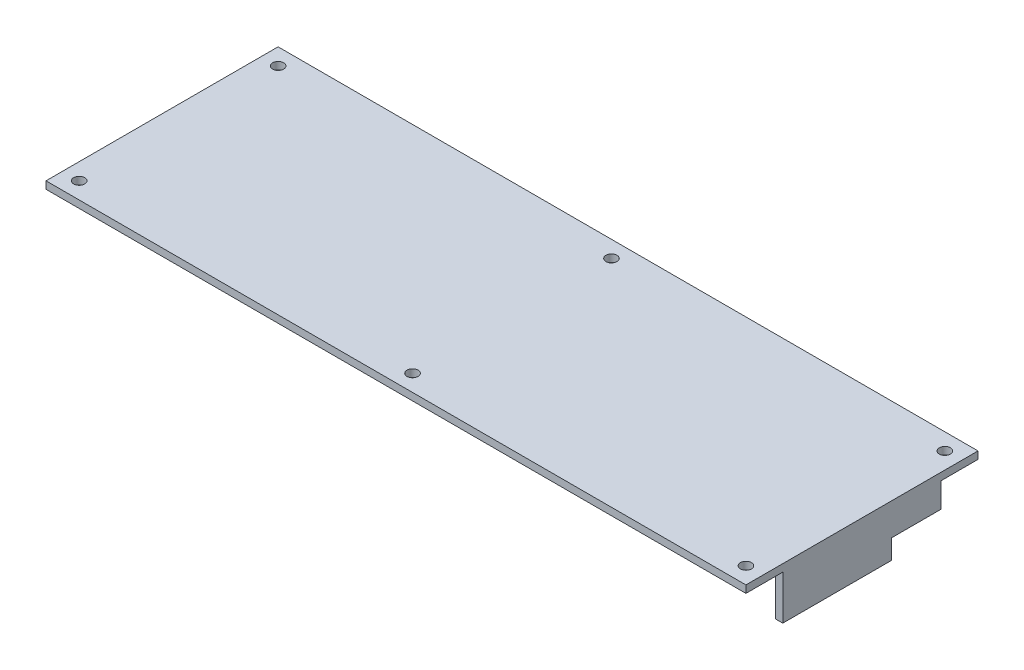
SolidWorks part; units mm, degrees
ref_plane "Front Plane" through (0, 0, 0) normal (0, 0, 1) x (1, 0, 0)
ref_plane "Top Plane" through (0, 0, 0) normal (0, 1, 0) x (1, 0, 0)
ref_plane "Right Plane" through (0, 0, 0) normal (1, 0, 0) x (0, 0, -1)
sketch "Sketch1" plane through (0, 0, 0) normal (0, 1, 0) x (1, 0, 0)
  line L0 (0, 15.9498) -> (0, -13.7203) construction
  line L9 (-95, -31.5) -> (95, -31.5)
  line L10 (-95, -31.5) -> (-95, 31.5)
  line L11 (-95, 31.5) -> (95, 31.5)
  line L12 (95, -31.5) -> (95, 31.5)
  line L13 (-95, -31.5) -> (95, 31.5) construction
  line L14 (-95, 31.5) -> (95, -31.5) construction
  line L15 (-95, 31.5) -> (-86, 31.5)
  line L16 (-95, 31.5) -> (-95, 22.5)
  line L17 (-93, 22.5) -> (-90.5, 22.5)
  line L18 (-86, 29.5) -> (-86, 27)
  line L19 (-23.9463, 0) -> (24.4289, 0) construction
  line L20 (93, 22.5) -> (90.5, 22.5)
  line L21 (86, 29.5) -> (86, 27)
  line L22 (95, 31.5) -> (86, 31.5)
  line L23 (95, 31.5) -> (95, 22.5)
  line L24 (95, -31.5) -> (86, -31.5)
  line L25 (86, -29.5) -> (86, -27)
  line L26 (93, -22.5) -> (90.5, -22.5)
  line L27 (95, -31.5) -> (95, -22.5)
  line L28 (-93, -22.5) -> (-90.5, -22.5)
  line L29 (-86, -29.5) -> (-86, -27)
  line L30 (-95, -31.5) -> (-86, -31.5)
  line L31 (-95, -31.5) -> (-95, -22.5)
  line L35 (-4.5, 31.5) -> (4.5, 31.5)
  line L37 (-4.5, 22.5) -> (4.5, 31.5) construction
  line L38 (-4.5, 31.5) -> (4.5, 22.5) construction
  line L42 (-95, 31.5) -> (-86, 22.5) construction
  line L43 (-95, 22.5) -> (-86, 31.5) construction
  line L44 (92, 29.5981) -> (93.5, 27)
  line L45 (-93.5, 27) -> (-92, 24.4019)
  line L46 (-92, 24.4019) -> (-89, 24.4019)
  line L47 (-89, 24.4019) -> (-87.5, 27)
  line L48 (-87.5, 27) -> (-89, 29.5981)
  line L49 (-89, 29.5981) -> (-92, 29.5981)
  line L50 (-92, 29.5981) -> (-93.5, 27)
  line L51 (89, 29.5981) -> (92, 29.5981)
  line L52 (87.5, 27) -> (89, 29.5981)
  line L53 (89, 24.4019) -> (87.5, 27)
  line L54 (92, 24.4019) -> (89, 24.4019)
  line L55 (93.5, 27) -> (92, 24.4019)
  line L56 (89, -29.5981) -> (92, -29.5981)
  line L57 (87.5, -27) -> (89, -29.5981)
  line L58 (89, -24.4019) -> (87.5, -27)
  line L59 (92, -24.4019) -> (89, -24.4019)
  line L60 (93.5, -27) -> (92, -24.4019)
  line L61 (92, -29.5981) -> (93.5, -27)
  line L62 (-92, -29.5981) -> (-93.5, -27)
  line L63 (-89, -29.5981) -> (-92, -29.5981)
  line L64 (-87.5, -27) -> (-89, -29.5981)
  line L65 (-89, -24.4019) -> (-87.5, -27)
  line L66 (-92, -24.4019) -> (-89, -24.4019)
  line L67 (-93.5, -27) -> (-92, -24.4019)
  line L80 (-4.5, 31.5) -> (-4.5, 22.5) construction
  line L81 (4.5, 31.5) -> (4.5, 22.5) construction
  line L82 (4.5, 22.5) -> (-4.5, 22.5) construction
  line L83 (-4.5, 29.5) -> (-4.5, 27)
  line L84 (4.5, 29.5) -> (4.5, 27)
  line L85 (4.5, -29.5) -> (4.5, -27)
  line L92 (-4.5, -29.5) -> (-4.5, -27)
  line L93 (1.5, -24.4019) -> (3, -27)
  line L94 (3, 27) -> (1.5, 29.5981)
  line L95 (1.5, 29.5981) -> (-1.5, 29.5981)
  line L96 (-1.5, 29.5981) -> (-3, 27)
  line L97 (-3, 27) -> (-1.5, 24.4019)
  line L98 (-1.5, 24.4019) -> (1.5, 24.4019)
  line L99 (1.5, 24.4019) -> (3, 27)
  line L106 (-1.5, -24.4019) -> (1.5, -24.4019)
  line L107 (-3, -27) -> (-1.5, -24.4019)
  line L108 (-1.5, -29.5981) -> (-3, -27)
  line L109 (1.5, -29.5981) -> (-1.5, -29.5981)
  line L110 (3, -27) -> (1.5, -29.5981)
  line L111 (-86, 29.5) -> (-4.5, 29.5)
  line L112 (-93, 22.5) -> (-93, -22.5)
  line L113 (-86, -29.5) -> (-4.5, -29.5)
  line L114 (4.5, -29.5) -> (86, -29.5)
  line L115 (93, -22.5) -> (93, 22.5)
  line L116 (86, 29.5) -> (4.5, 29.5)
  circle A0 centre (-90.5, 27) radius 1.5
  circle A1 centre (-90.5, 27) radius 2.5981 construction
  circle A2 centre (90.5, 27) radius 1.5
  circle A3 centre (90.5, -27) radius 1.5
  circle A4 centre (-90.5, -27) radius 1.5
  circle A5 centre (0, 27) radius 1.5
  circle A6 centre (0, 27) radius 2.5981 construction
  arc A8 (-90.5, 22.5) -> (-86, 27) centre (-90.5, 27) ccw
  arc A9 (-4.5, 27) -> (4.5, 27) centre (0, 27) ccw
  circle A10 centre (0, -27) radius 1.5
  arc A11 (-4.5, -27) -> (4.5, -27) centre (0, -27) cw
  arc A12 (-86, -27) -> (-90.5, -22.5) centre (-90.5, -27) ccw
  arc A13 (86, -27) -> (90.5, -22.5) centre (90.5, -27) cw
  arc A14 (86, 27) -> (90.5, 22.5) centre (90.5, 27) ccw
  point P0 (0, 0)
  point P22 (0, 27)
  point P27 (0, 31.5)
  point P28 (0, 31.5)
  point P91 (-86, -22.5)
  point P94 (86, -22.5)
  point P97 (86, 22.5)
  dimension "D7" = 3
  dimension "D10" = 3
  dimension "D13" = 4.5
  dimension "D14" = 4.5
  dimension "D15" = 4.5
  dimension "D16" = 4.5
  dimension "D17" = 2
  dimension "D11" = 6
  dimension "D1" = 190
  dimension "D2" = 63
  dimension "D3" = 9
  dimension "D4" = 9
  dimension "D5" = 9
  dimension "D6" = 9
  dimension "D8" = 6
  dimension "D9" = 1.5
  dimension "D12" = 1.5
  dimension "D18" = 2
  dimension "D19" = 2
  dimension "D20" = 2
  dimension "D21" = 2
  dimension "D22" = 2
  dimension "D23" = 4.5
  dimension "D24" = 4.5
  dimension "D25" = 2
  dimension "D26" = 2
  dimension "D27" = 2
  dimension "D28" = 2
  dimension "D29" = 4.5
  dimension "D30" = 4.5
  dimension "D31" = 2
  dimension "D32" = 2
extrude "Boss-Extrude1" add sketch "Sketch1" along normal blind 2 contours A14 L21 L116 L84 A9 L83 L111 L18 A8 L17 L112 L28 A12 L29 L113 L92 A11 L85 L114 L25 A13 L26 L115 L20 region at (0, 0, 0)
extrude "Boss-Extrude2" add sketch "Sketch1<4>" along normal blind 19 separate body contours A2 | A3 | A10 | A5 | A0 | A4 region at (-90.5, 0, -27) region at (90.5, 0, -27) region at (90.5, 0, 27) region at (0, 0, -27) region at (0, 0, 27)
sketch "Sketch1<4>" plane through (0, 0, 0) normal (0, 1, 0) x (1, 0, 0) same geometry as "Sketch1"
extrude "Boss-Extrude3" add sketch "Sketch1<5>" along normal blind 20 contours L55 L44 L51 L52 L53 L54 A2 | L56 L61 L60 L59 L58 L57 A3 | L110 L93 L106 L107 L108 L109 A10 | L98 L99 L94 L95 L96 L97 A5 | L67 L62 L63 L64 L65 L66 A4 | L49 L50 L45 L46 L47 L48 A0 region at (92.6813, 0, -28.2594) region at (-92.6813, 0, -28.2594) region at (88.3187, 0, 28.2594) region at (-92.6813, 0, 28.2594) region at (2.1813, 0, 25.7406) region at (2.1813, 0, -25.7406)
sketch "Sketch1<5>" plane through (0, 0, 0) normal (0, 1, 0) x (1, 0, 0) same geometry as "Sketch1"
extrude "Boss-Extrude4" add sketch "Sketch1<6>" along normal blind 22 contours L9 L12 L11 L10 L99 L98 L97 L96 L95 L94 L61 L56 L57 L58 L59 L60 L50 L49 L48 L47 L46 L45 L44 L55 L54 L53 L52 L51 L62 L67 L66 L65 L64 L63 L93 region at (-94.7998, 0, 27)
sketch "Sketch1<6>" plane through (0, 0, 0) normal (0, 1, 0) x (1, 0, 0) same geometry as "Sketch1"
sketch "Sketch2" plane through (95, 0, 0) normal (1, 0, 0) x (0, 0, -1)
  line L0 (-22.5, 2) -> (22.5, 2) construction
  line L1 (-22.5, 12.0332) -> (-22.5, 2) construction
  line L2 (-31.5, 22) -> (-31.5, 0) construction
  line L3 (-31.5, 0) -> (31.5, 0) construction
  line L4 (31.5, 22) -> (31.5, 0) construction
  line L5 (-21.5, 2) -> (1.5, 2)
  line L6 (-21.5, 2) -> (-21.5, 10)
  line L7 (-21.5, 10) -> (1.5, 10)
  line L8 (1.5, 2) -> (1.5, 10)
  line L10 (8, 2) -> (21.5, 2)
  line L11 (8, 2) -> (8, 15.3)
  line L12 (8, 15.3) -> (21.5, 15.3)
  line L13 (21.5, 2) -> (21.5, 15.3)
  dimension "D1" = 9
  dimension "D2" = 2
  dimension "D3" = 9
  dimension "D4" = 23
  dimension "D5" = 8
  dimension "D6" = 10
  dimension "D7" = 13.3
  dimension "D8" = 13.5
  dimension "D9" = 10
extrude "Cut-Extrude1" cut sketch "Sketch2" against normal blind 3
sketch "Sketch3" plane through (0, 0, -31.5) normal (0, 0, -1) x (-1, 0, 0)
  line L0 (-95, 22) -> (-95, 0) construction
  line L1 (-75, 2) -> (-55, 2)
  line L2 (-75, 2) -> (-75, 14)
  line L3 (-75, 14) -> (-55, 14)
  line L4 (-55, 2) -> (-55, 14)
  line L5 (95, 0) -> (-95, 0) construction
  line L6 (95, 22) -> (95, 0) construction
  line L7 (35, 2) -> (68, 2)
  line L8 (35, 2) -> (35, 14)
  line L9 (35, 14) -> (68, 14)
  line L10 (68, 2) -> (68, 14)
  dimension "D1" = 20
  dimension "D2" = 20
  dimension "D3" = 2
  dimension "D4" = 12
  dimension "D5" = 60
  dimension "D6" = 33
  dimension "D7" = 2
  dimension "D8" = 12
extrude "Cut-Extrude2" cut sketch "Sketch3" against normal blind 3
sketch "Sketch4" plane through (-95, 0, 0) normal (-1, 0, 0) x (0, 0, 1)
  line L0 (0, 0) -> (0, 22) construction
  line L1 (31.5, 22) -> (-31.5, 22) construction
  line L2 (31.5, 0) -> (-31.5, 0) construction
  line L3 (-15.5, 2) -> (-3.5, 2)
  line L4 (-15.5, 2) -> (-15.5, 9.5)
  line L5 (-15.5, 9.5) -> (-3.5, 9.5)
  line L6 (-3.5, 2) -> (-3.5, 9.5)
  line L7 (-31.5, 22) -> (-31.5, 0) construction
  line L8 (15.5, 9.5) -> (3.5, 9.5)
  line L9 (3.5, 2) -> (3.5, 9.5)
  line L10 (15.5, 2) -> (3.5, 2)
  line L11 (15.5, 2) -> (15.5, 9.5)
  dimension "D1" = 2
  dimension "D2" = 12
  dimension "D3" = 7.5
  dimension "D4" = 16
extrude "Cut-Extrude3" cut sketch "Sketch4" against normal blind 3
sketch "Sketch5" plane through (95, 0, 0) normal (1, 0, 0) x (0, 0, -1)
  line L0 (-21.5, 10) -> (-21.5, 22)
  line L1 (-31.5, 22) -> (31.5, 22) construction
  line L2 (-21.5, 10) -> (8, 10)
  line L3 (8, 15.3) -> (8, 2) construction
  line L4 (8, 10) -> (8, 15.3)
  line L5 (8, 15.3) -> (21.5, 15.3)
  line L6 (21.5, 15.3) -> (21.5, 22)
  line L7 (-21.5, 22) -> (-31.5, 22)
  line L8 (-31.5, 22) -> (-31.5, 0)
  line L9 (-31.5, 0) -> (31.5, 0)
  line L10 (31.5, 0) -> (31.5, 22)
  line L11 (31.5, 22) -> (21.5, 22)
sketch "Sketch6" plane through (0, 0, -31.5) normal (0, 0, -1) x (-1, 0, 0)
  line L0 (-75, 22) -> (-75, 14)
  line L1 (95, 22) -> (-95, 22) construction
  line L2 (-75, 14) -> (-55, 14)
  line L3 (35, 14) -> (35, 22)
  line L4 (68, 14) -> (68, 22)
  line L5 (-55, 14) -> (-55, 22)
  line L6 (68, 14) -> (35, 14) construction
  line L7 (68, 2) -> (68, 14) construction
  line L8 (-75, 14) -> (-75, 2) construction
  line L9 (35, 14) -> (68, 14)
  line L10 (-75, 22) -> (-95, 22)
  line L11 (-95, 22) -> (-95, 0)
  line L12 (-95, 0) -> (95, 0)
  line L13 (95, 0) -> (95, 22)
  line L14 (95, 22) -> (68, 22)
  line L15 (-55, 22) -> (35, 22)
sketch "Sketch7" plane through (-95, 0, 0) normal (-1, 0, 0) x (0, 0, 1)
  line L0 (-15.5, 9.5) -> (-15.5, 22)
  line L1 (31.5, 22) -> (-31.5, 22) construction
  line L2 (-15.5, 9.5) -> (15.5, 9.5)
  line L3 (15.5, 9.5) -> (15.5, 22)
  line L4 (15.5, 9.5) -> (3.5, 9.5) construction
  line L5 (15.5, 2) -> (15.5, 9.5) construction
  line L6 (-15.5, 22) -> (-31.5, 22)
  line L7 (-31.5, 22) -> (-31.5, 0)
  line L8 (-31.5, 0) -> (31.5, 0)
  line L9 (31.5, 0) -> (31.5, 22)
  line L10 (31.5, 22) -> (15.5, 22)
sketch "Sketch9" plane through (0, 0, 31.5) normal (0, 0, 1) x (1, 0, 0)
  line L1 (-95, 22) -> (95, 22)
  line L2 (-95, 22) -> (-95, 0)
  line L3 (-95, 0) -> (95, 0)
  line L4 (95, 22) -> (95, 0)
sketch "Sketch10" plane through (0, 22, 0) normal (0, 1, 0) x (1, 0, 0)
  line L0 (-93, 29.5) -> (93, 29.5)
  line L1 (-95, 31.5) -> (95, 31.5)
  line L2 (-95, 31.5) -> (-95, -31.5)
  line L3 (-95, -31.5) -> (95, -31.5)
  line L4 (95, 31.5) -> (95, -31.5)
  line L5 (93, 29.5) -> (93, -29.5)
  line L6 (-93, -29.5) -> (93, -29.5)
  line L7 (-93, 29.5) -> (-93, -29.5)
  dimension "D1" = 2
extrude "Boss-Extrude5" add sketch "Sketch10" along normal blind 2 contours L0 L7 L6 L5 | L4 L1 L2 L3 L7 L0 L5 L6 region at (0, 22, 0) region at (0, 22, -31.2998)
extrude "Cut-Extrude7" cut sketch "Sketch10<3>" against normal blind 22 contours L0 L7 L6 L5 region at (0, 22, 0)
sketch "Sketch10<3>" plane through (0, 22, 0) normal (0, 1, 0) x (1, 0, 0) same geometry as "Sketch10"
extrude "Cut-Extrude8" cut sketch "Sketch5" against normal blind 2
extrude "Cut-Extrude9" cut sketch "Sketch6" against normal blind 2
extrude "Cut-Extrude10" cut sketch "Sketch7" against normal blind 2
extrude "Cut-Extrude11" cut sketch "Sketch9" against normal blind 2
extrude "Cut-Extrude12" cut sketch "Sketch1<7>" along normal blind 24 contours A4 | A0 | A3 | A2 | A10 | A5 region at (-90.5, 0, -27) region at (90.5, 0, -27) region at (90.5, 0, 27) region at (-90.5, 0, 27) region at (0, 0, -27) region at (0, 0, 27)
sketch "Sketch1<7>" plane through (0, 0, 0) normal (0, 1, 0) x (1, 0, 0) same geometry as "Sketch1"
